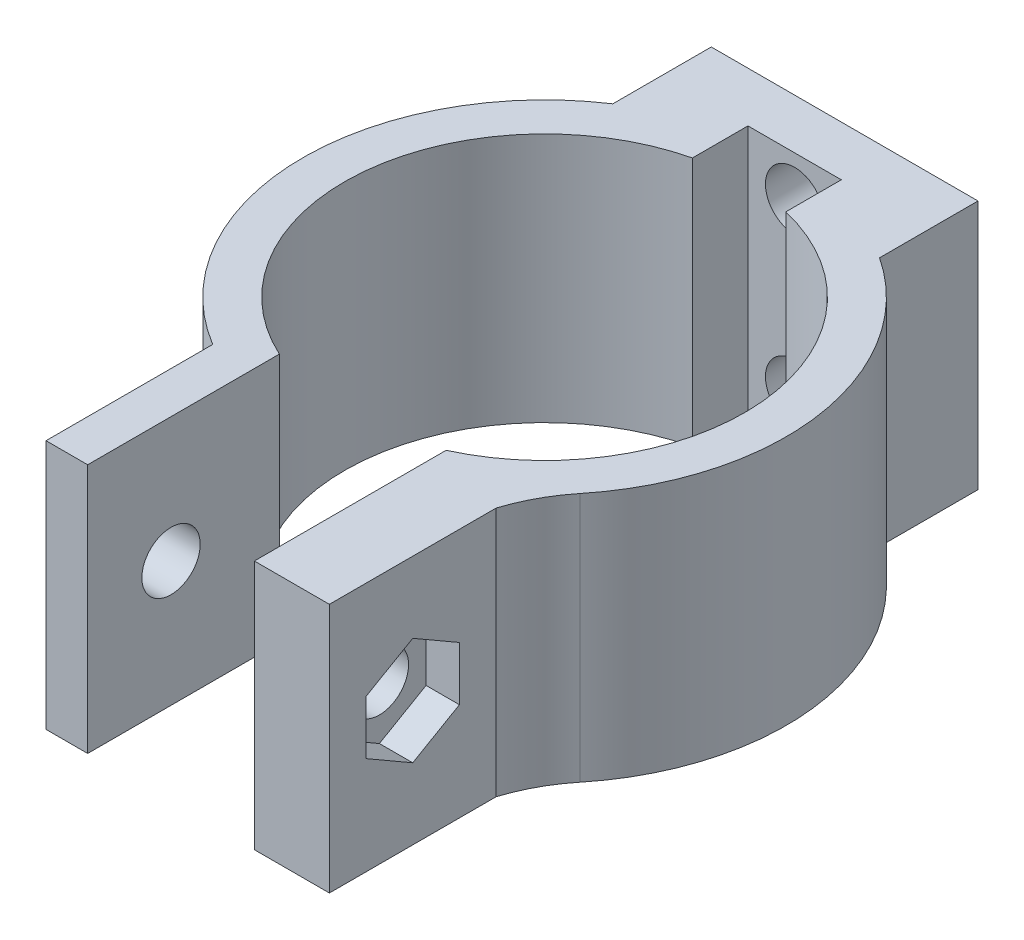
SolidWorks part; units mm, degrees
ref_plane "Plano frontal" through (0, 0, 0) normal (0, 0, 1) x (1, 0, 0)
ref_plane "Plano superior" through (0, 0, 0) normal (0, 1, 0) x (1, 0, 0)
ref_plane "Plano direito" through (0, 0, 0) normal (1, 0, 0) x (0, 0, -1)
sketch "Esboço13" plane through (0, 0, 0) normal (0, 1, 0) x (1, 0, 0)
  line L0 (5, -10.9087) -> (5, -22.4097)
  line L1 (5, -22.4097) -> (7.5, -22.4097)
  line L2 (7.5, -22.4097) -> (7.5, -12.4097)
  line L3 (0, 23.3485) -> (0, 0) construction
  line L4 (8, 12.0934) -> (8, 18)
  line L5 (8, 18) -> (-8, 18)
  line L6 (0, 16.3485) -> (0, 15.3485)
  line L7 (-8, 12.0934) -> (-8, 18)
  line L8 (-7.5, -22.4097) -> (-7.5, -12.4097)
  line L9 (-5, -22.4097) -> (-7.5, -22.4097)
  line L10 (-5, -10.9087) -> (-5, -22.4097)
  line L11 (-2.8, 11.6688) -> (-2.8, 15)
  line L12 (-2.8, 15) -> (2.8, 15)
  line L13 (2.8, 11.6688) -> (2.8, 15)
  arc A0 (7.5, -12.4097) -> (8, 12.0934) centre (0, 0) ccw
  arc A1 (5, -10.9087) -> (2.8, 11.6688) centre (0, 0) ccw
  arc A2 (-7.5, -12.4097) -> (-8, 12.0934) centre (0, 0) cw
  arc A3 (-2.8, 11.6688) -> (-5, -10.9087) centre (0, 0) ccw
  point P22 (0, 15)
  dimension "D3" = 12
  dimension "D1" = 2.5
  dimension "D4" = 6
  dimension "D2" = 2.5
  dimension "D5" = 10
  dimension "D6" = 10
  dimension "D7" = 16
  dimension "D8" = 5.6
  dimension "D9" = 3
extrude "Ressalto-extrusão6" add sketch "Esboço13" along normal blind 15 contours L3 L5 L7 A2 L8 L9 L10 A3 L11 L12 L6 | L5 L3 L6 L12 L13 A1 L0 L1 L2 A0 L4
sketch "Esboço14" plane through (0, 0, -18) normal (0, 0, -1) x (-1, 0, 0)
  line L0 (-8, 7.5) -> (8, 7.5) construction
  line L1 (-8, 15) -> (-8, 0) construction
  line L2 (8, 15) -> (8, 0) construction
  circle A0 centre (0, 12.5) radius 1.75
  circle A1 centre (0, 2.5) radius 1.75
  point P10 (0, 0)
  point P11 (0, 0)
  point P12 (0, 0)
  dimension "D2" = 3.5
  dimension "D1" = 10
extrude "Corte-extrusão1" cut sketch "Esboço14" against normal through all both and the other way through all
sketch "Esboço15" plane through (7.5, 0, 0) normal (1, 0, 0) x (0, 0, -1)
  line L0 (-22.4097, 15) -> (-12.4097, 0) construction
  circle A0 centre (-17.4097, 7.5) radius 1.75
  dimension "D1" = 3.5
extrude "Corte-extrusão2" cut sketch "Esboço15" against normal through all
sketch "Esboço17" plane through (7.5, 0, 0) normal (1, 0, 0) x (0, 0, -1)
  line L1 (-17.4097, 10.7332) -> (-20.2097, 9.1166)
  line L2 (-20.2097, 9.1166) -> (-20.2097, 5.8834)
  line L3 (-20.2097, 5.8834) -> (-17.4097, 4.2668)
  line L4 (-17.4097, 4.2668) -> (-14.6097, 5.8834)
  line L5 (-14.6097, 5.8834) -> (-14.6097, 9.1166)
  line L6 (-14.6097, 9.1166) -> (-17.4097, 10.7332)
  line L10 (-22.4097, 0) -> (-12.4097, 0)
  line L11 (-12.4097, 0) -> (-12.4097, 15)
  line L12 (-12.4097, 15) -> (-22.4097, 15)
  line L13 (-22.4097, 15) -> (-22.4097, 0)
  line L14 (-22.4097, 0) -> (-12.4097, 0)
  line L15 (-12.4097, 0) -> (-12.4097, 15)
  line L16 (-12.4097, 15) -> (-22.4097, 15)
  line L17 (-22.4097, 15) -> (-22.4097, 0)
  circle A0 centre (-17.4097, 7.5) radius 2.8 construction
  dimension "D1" = 5.6
  dimension "D2" = 0
extrude "Ressalto-extrusão7" add sketch "Esboço17" along normal blind 2
fillet "Filete1" radius 10 1 edges at (7.5, 7.5, 12.4097)
